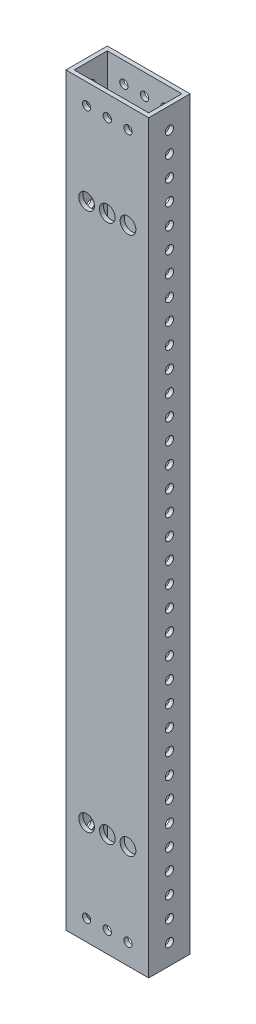
SolidWorks part; units mm, degrees
ref_plane "Front Plane" through (0, 0, 0) normal (0, 0, 1) x (1, 0, 0)
ref_plane "Top Plane" through (0, 0, 0) normal (0, 1, 0) x (1, 0, 0)
ref_plane "Right Plane" through (0, 0, 0) normal (1, 0, 0) x (0, 0, -1)
sketch "Sketch1" plane through (0, 0, 0) normal (0, 1, 0) x (1, 0, 0)
  line L1 (-46.8721, 24.2038) -> (3.9279, 24.2038)
  line L2 (-46.8721, 24.2038) -> (-46.8721, -1.1962)
  line L3 (-46.8721, -1.1962) -> (3.9279, -1.1962)
  line L4 (3.9279, 24.2038) -> (3.9279, -1.1962)
  line L5 (-46.8721, 24.2038) -> (3.9279, -1.1962) construction
  line L6 (-46.8721, -1.1962) -> (3.9279, 24.2038) construction
  line L7 (-44.3321, 21.6638) -> (1.3879, 21.6638)
  line L8 (-44.3321, 21.6638) -> (-44.3321, 1.3438)
  line L9 (-44.3321, 1.3438) -> (1.3879, 1.3438)
  line L10 (1.3879, 21.6638) -> (1.3879, 1.3438)
  line L11 (-44.3321, 21.6638) -> (1.3879, 1.3438) construction
  line L12 (-44.3321, 1.3438) -> (1.3879, 21.6638) construction
  point P0 (-21.4721, 11.5038)
  point P5 (-21.4721, 11.5038)
  dimension "D1" = 2.54
  dimension "D2" = 2.54
  dimension "D3" = 25.4
  dimension "D4" = 50.8
extrude "Boss-Extrude1" add sketch "Sketch1" along normal blind 457.2
sketch "Sketch3" plane through (3.9279, 0, 0) normal (1, 0, 0) x (0, 0, -1)
  line L0 (-1.1962, 457.2) -> (24.2038, 457.2) construction
  line L2 (24.2038, 457.2) -> (24.2038, 0) construction
  circle A0 centre (11.5038, 444.246) radius 2.54
  circle A1 centre (11.5038, 431.546) radius 2.54
  circle A2 centre (11.5038, 418.846) radius 2.54
  circle A3 centre (11.5038, 406.146) radius 2.54
  circle A4 centre (11.5038, 393.446) radius 2.54
  circle A5 centre (11.5038, 380.746) radius 2.54
  circle A6 centre (11.5038, 368.046) radius 2.54
  circle A7 centre (11.5038, 355.346) radius 2.54
  circle A8 centre (11.5038, 342.646) radius 2.54
  circle A9 centre (11.5038, 329.946) radius 2.54
  circle A10 centre (11.5038, 317.246) radius 2.54
  circle A11 centre (11.5038, 304.546) radius 2.54
  circle A12 centre (11.5038, 291.846) radius 2.54
  circle A13 centre (11.5038, 279.146) radius 2.54
  circle A14 centre (11.5038, 266.446) radius 2.54
  circle A15 centre (11.5038, 253.746) radius 2.54
  circle A16 centre (11.5038, 241.046) radius 2.54
  circle A17 centre (11.5038, 228.346) radius 2.54
  circle A18 centre (11.5038, 215.646) radius 2.54
  circle A19 centre (11.5038, 202.946) radius 2.54
  circle A20 centre (11.5038, 190.246) radius 2.54
  circle A21 centre (11.5038, 177.546) radius 2.54
  circle A22 centre (11.5038, 164.846) radius 2.54
  circle A23 centre (11.5038, 152.146) radius 2.54
  circle A24 centre (11.5038, 139.446) radius 2.54
  circle A25 centre (11.5038, 126.746) radius 2.54
  circle A26 centre (11.5038, 114.046) radius 2.54
  circle A27 centre (11.5038, 101.346) radius 2.54
  circle A28 centre (11.5038, 88.646) radius 2.54
  circle A29 centre (11.5038, 75.946) radius 2.54
  circle A30 centre (11.5038, 63.246) radius 2.54
  circle A31 centre (11.5038, 50.546) radius 2.54
  circle A32 centre (11.5038, 37.846) radius 2.54
  circle A33 centre (11.5038, 25.146) radius 2.54
  circle A34 centre (11.5038, 12.446) radius 2.54
  dimension "D3" = 5.08
  dimension "D1" = 12.954
  dimension "D2" = 12.7
  dimension "D4" = 35
extrude "Cut-Extrude1" cut sketch "Sketch3" against normal blind 457.2
sketch "Sketch4" plane through (0, 0, -24.2038) normal (0, 0, -1) x (-1, 0, 0)
  line L0 (-3.9279, 457.2) -> (46.8721, 457.2) construction
  line L1 (46.8721, 457.2) -> (46.8721, 0) construction
  line L2 (-3.9279, 457.2) -> (-3.9279, 0) construction
  line L4 (-3.9279, 228.6) -> (46.8721, 228.6) construction
  circle A0 centre (34.1721, 444.5) radius 2.54
  circle A1 centre (21.4721, 444.5) radius 2.54
  circle A2 centre (8.7721, 444.5) radius 2.54
  circle A3 centre (8.7721, 393.7) radius 4.826
  circle A4 centre (21.4721, 393.7) radius 4.826
  circle A5 centre (34.1721, 393.7) radius 4.826
  circle A6 centre (34.1721, 12.7) radius 2.54
  circle A7 centre (21.4721, 12.7) radius 2.54
  circle A8 centre (8.7721, 12.7) radius 2.54
  circle A9 centre (34.1721, 63.5) radius 4.826
  circle A10 centre (21.4721, 63.5) radius 4.826
  circle A11 centre (8.7721, 63.5) radius 4.826
  dimension "D1" = 5.08
  dimension "D6" = 9.652
  dimension "D2" = 12.7
  dimension "D3" = 12.7
  dimension "D5" = 50.8
  dimension "D7" = 12.7
  dimension "D4" = 3
  dimension "D8" = 3
extrude "Cut-Extrude3" cut sketch "Sketch4" against normal blind 457.2
